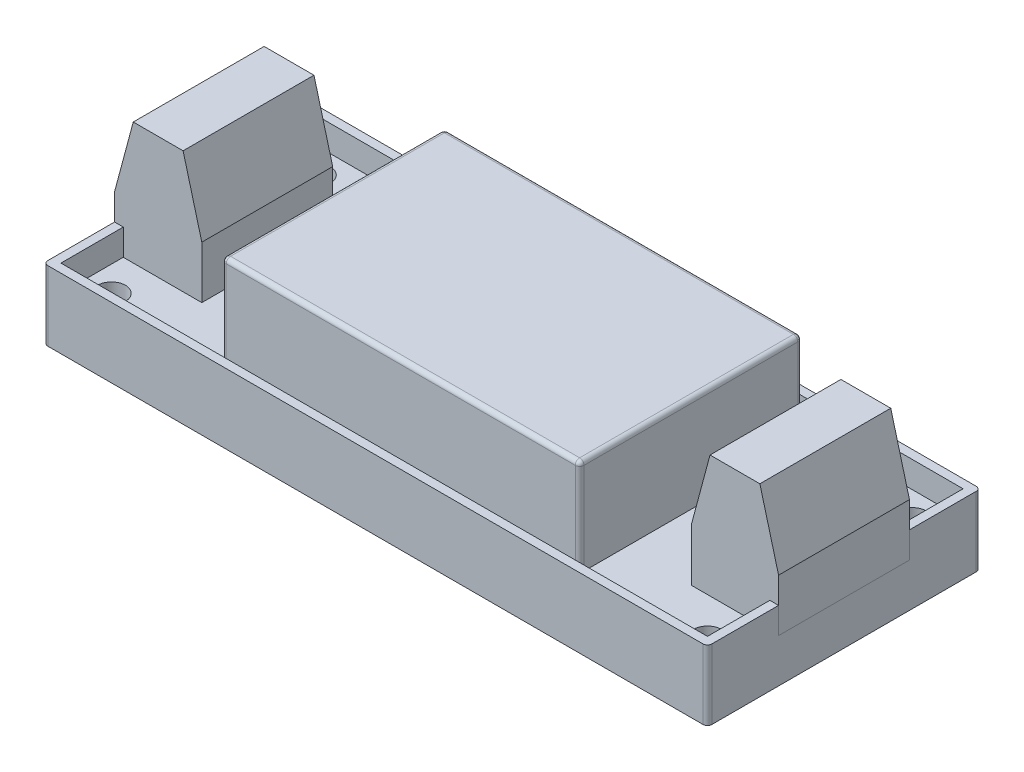
SolidWorks part; units mm, degrees
ref_plane "Front Plane" through (0, 0, 0) normal (0, 0, 1) x (1, 0, 0)
ref_plane "Top Plane" through (0, 0, 0) normal (0, 1, 0) x (1, 0, 0)
ref_plane "Right Plane" through (0, 0, 0) normal (1, 0, 0) x (0, 0, -1)
sketch "Sketch1" plane through (0, 0, 0) normal (0, 1, 0) x (1, 0, 0)
  line L0 (35.75, 11.75) -> (38.05, 11.75) construction
  line L1 (-38.05, -15.65) -> (38.05, -15.65)
  line L2 (-38.05, -15.65) -> (-38.05, 15.65)
  line L3 (-38.05, 15.65) -> (38.05, 15.65)
  line L4 (38.05, -15.65) -> (38.05, 15.65)
  line L5 (-38.05, -15.65) -> (38.05, 15.65) construction
  line L6 (-38.05, 15.65) -> (38.05, -15.65) construction
  line L7 (-34.15, -11.75) -> (34.15, -11.75) construction
  line L8 (-34.15, -11.75) -> (-34.15, 11.75) construction
  line L9 (-34.15, 11.75) -> (34.15, 11.75) construction
  line L10 (34.15, -11.75) -> (34.15, 11.75) construction
  line L11 (-34.15, -11.75) -> (34.15, 11.75) construction
  line L12 (-34.15, 11.75) -> (34.15, -11.75) construction
  line L13 (34.15, 13.35) -> (34.15, 15.65) construction
  circle A0 centre (34.15, 11.75) radius 1.6
  circle A1 centre (34.15, -11.75) radius 1.6
  circle A2 centre (-34.15, -11.75) radius 1.6
  circle A3 centre (-34.15, 11.75) radius 1.6
  point P0 (0, 0)
  point P6 (0, 0)
  dimension "D3" = 3.2
  dimension "D1" = 76.1
  dimension "D2" = 31.3
  dimension "D4" = 2.3
extrude "Boss-Extrude1" add sketch "Sketch1" along normal blind 5
sketch "Sketch2" plane through (0, 5, 0) normal (0, 1, 0) x (1, 0, 0)
  line L0 (38.05, -15.65) -> (38.05, 15.65) construction
  line L1 (-38.05, -15.65) -> (38.05, -15.65) construction
  line L2 (-38.05, 15.65) -> (-38.05, -15.65) construction
  line L3 (38.05, 15.65) -> (-38.05, 15.65) construction
  line L4 (38.05, -15.65) -> (38.05, 15.65)
  line L5 (-38.05, -15.65) -> (38.05, -15.65)
  line L6 (-38.05, 15.65) -> (-38.05, -15.65)
  line L7 (38.05, 15.65) -> (-38.05, 15.65)
  line L8 (-37.05, 14.65) -> (-37.05, 15.65) construction
  line L9 (37.05, -14.65) -> (-37.05, -14.65)
  line L10 (37.05, -14.65) -> (37.05, 14.65)
  line L11 (37.05, 14.65) -> (-37.05, 14.65)
  line L12 (-37.05, -14.65) -> (-37.05, 14.65)
  line L13 (37.05, -14.65) -> (-37.05, 14.65) construction
  line L14 (37.05, 14.65) -> (-37.05, -14.65) construction
  line L15 (-37.05, 14.65) -> (-38.05, 14.65) construction
  line L16 (0, 0) -> (0, 15.65) construction
  line L17 (20.5, -12.75) -> (-20.5, -12.75)
  line L18 (20.5, -12.75) -> (20.5, 12.75)
  line L19 (20.5, 12.75) -> (-20.5, 12.75)
  line L20 (-20.5, -12.75) -> (-20.5, 12.75)
  line L21 (20.5, -12.75) -> (-20.5, 12.75) construction
  line L22 (20.5, 12.75) -> (-20.5, -12.75) construction
  line L23 (28.05, -7.5) -> (38.05, -7.5)
  line L24 (28.05, -7.5) -> (28.05, 7.5)
  line L25 (28.05, 7.5) -> (38.05, 7.5)
  line L26 (38.05, -7.5) -> (38.05, 7.5)
  line L27 (28.05, -7.5) -> (38.05, 7.5) construction
  line L28 (28.05, 7.5) -> (38.05, -7.5) construction
  line L29 (-28.05, -7.5) -> (-38.05, -7.5)
  line L30 (-28.05, -7.5) -> (-28.05, 7.5)
  line L31 (-28.05, 7.5) -> (-38.05, 7.5)
  point P3 (0, 0)
  point P10 (0, 0)
  point P17 (33.05, 0)
  point P24 (0, 0)
  line M20 (38.05, -15.65) -> (38.05, 15.65)
  line M21 (38.05, 15.65) -> (-38.05, 15.65)
  line M22 (-38.05, 15.65) -> (-38.05, -15.65)
  line M23 (-38.05, -15.65) -> (38.05, -15.65)
  dimension "D1" = 1
  dimension "D2" = 41
  dimension "D3" = 25.5
  dimension "D4" = 15
  dimension "D5" = 10
extrude "Boss-Extrude2" add sketch "Sketch2" along normal blind 3 contours L31 L12 L11 L10 L25 M20 M21 M22 | L12 L29 L6 L23 L10 L9 M23 M20 region at (0, 5, 14.8846) region at (37.55, 5, -8.2654)
extrude "Boss-Extrude3" add sketch "Sketch2<3>" along normal blind 11 contours L20 L17 L18 L19 region at (0, 5, 0)
sketch "Sketch2<3>" plane through (0, 5, 0) normal (0, 1, 0) x (1, 0, 0) same geometry as "Sketch2"
extrude "Boss-Extrude4" add sketch "Sketch2<4>" along normal blind 14 separate body contours L30 L31 L12 L29 | L12 L31 L6 L29 | L25 L24 L23 L10 | L25 L10 L23 L4 region at (37.55, 5, 0) region at (32.55, 5, 0) region at (-37.55, 5, 0) region at (-32.55, 5, 0)
sketch "Sketch2<4>" plane through (0, 5, 0) normal (0, 1, 0) x (1, 0, 0) same geometry as "Sketch2"
fillet "Fillet1" radius 0.5 12 edges at (0, 16, -12.75) (-20.5, 16, 0) (0, 16, 12.75) (20.5, 16, 0) (20.5, 10.5, 12.75) (20.5, 10.5, -12.75) (-20.5, 10.5, -12.75) (-20.5, 10.5, 12.75) (-38.05, 4, 15.65) (-38.05, 4, -15.65) (38.05, 4, -15.65) (38.05, 4, 15.65)
chamfer "Chamfer1" distance 8 angle 15 2 edges at (-28.05, 19, 0) (-38.05, 19, 0) first distance on face at (-28.05, 12, 0) first distance on face at (-38.05, 12, 0)
chamfer "Chamfer2" distance 8 angle 15 2 edges at (38.05, 19, 0) (28.05, 19, 0) first distance on face at (38.05, 12, 0) first distance on face at (28.05, 12, 0)
